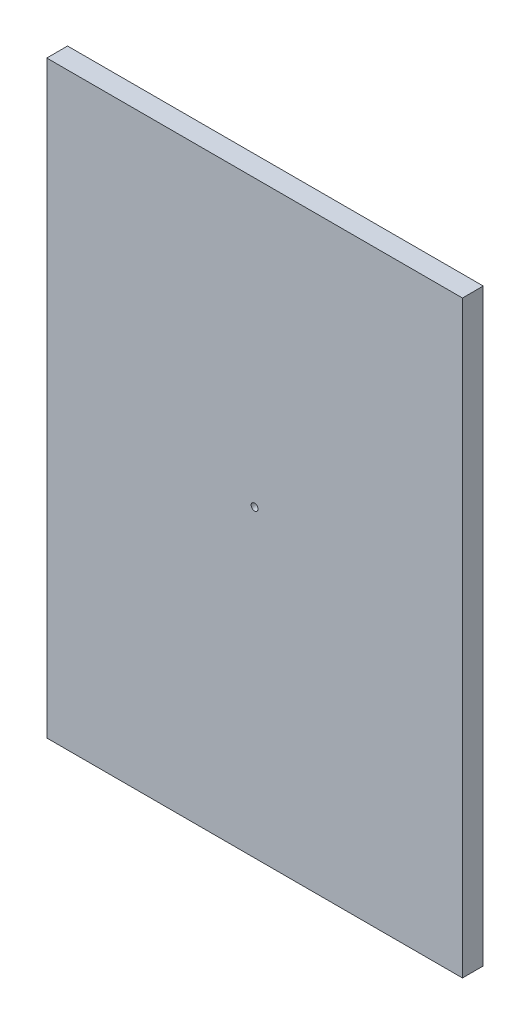
SolidWorks part; units mm, degrees
material "Glass"
ref_plane "Front Plane" through (0, 0, 0) normal (0, 0, 1) x (1, 0, 0)
ref_plane "Top Plane" through (0, 0, 0) normal (0, 1, 0) x (1, 0, 0)
ref_plane "Right Plane" through (0, 0, 0) normal (1, 0, 0) x (0, 0, -1)
sketch "Sketch1" plane through (0, 0, 0) normal (0, 0, 1) x (1, 0, 0)
  line L0 (30, -42.5) -> (30, -41.14) construction
  line L1 (0, 0) -> (60, 0)
  line L2 (0, 0) -> (0, -85)
  line L3 (0, -85) -> (60, -85)
  line L4 (60, 0) -> (60, -85)
  circle A0 centre (30, -42.5) radius 0.5
  circle A1 centre (30, -41.14) radius 0.5
  point P7 (60, -42.5)
  point P8 (30, 0)
  dimension "D3" = 1
  dimension "D1" = 60
  dimension "D2" = 85
  dimension "D4" = 1.36
extrude "Boss-Extrude1" add sketch "Sketch1" along normal blind 3 contours L4 L1 L2 L3 A0 A1 | A0 region at (30, -1.0404, 0) region at (30, -42.5, 0)
ref_plane "Plane1" through (30, 0, 0) normal (1, 0, 0) x (0, 0, -1)
sketch "Sketch2" plane through (30, 0, 0) normal (1, 0, 0) x (0, 0, -1)
  line L1 (-3, -42.5) -> (-8, -42.5) construction
  line L2 (-3, -41.14) -> (-215.132, 170.992) construction
  line L3 (-3, -41.14) -> (-8, -41.14) construction
  line L4 (-3, 0) -> (-3, -85) construction
  dimension "D1" = 5
  dimension "D3" = 45
  dimension "D4" = 300
equation "\"D4@Sketch1\"=1.36"
